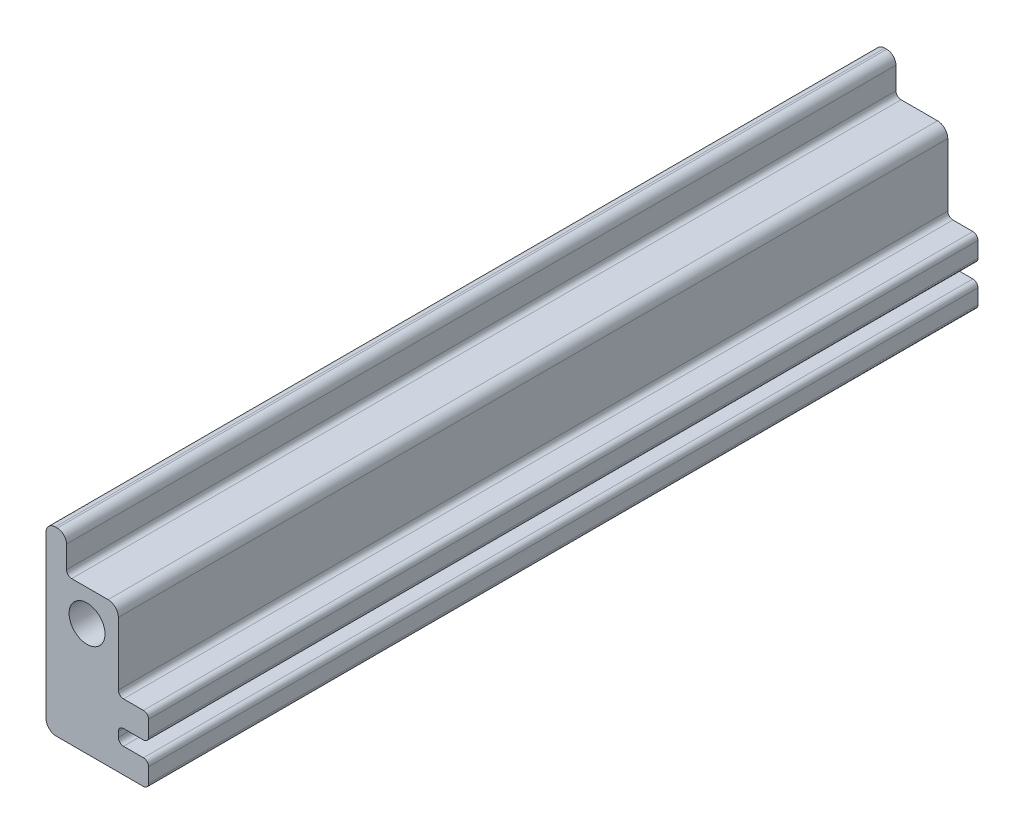
SolidWorks part; units mm, degrees
material "Pink Foam"
ref_plane "Front Plane" through (0, 0, 0) normal (0, 0, 1) x (1, 0, 0)
ref_plane "Top Plane" through (0, 0, 0) normal (0, 1, 0) x (1, 0, 0)
ref_plane "Right Plane" through (0, 0, 0) normal (1, 0, 0) x (0, 0, -1)
sketch "Sketch1" plane through (0, 0, 0) normal (0, 0, 1) x (1, 0, 0)
  line L1 (34.925, -69.85) -> (-19.05, -69.85)
  line L2 (38.1, -41.7472) -> (38.1, -32.2222)
  line L3 (34.925, -29.0472) -> (22.5628, -29.0472)
  line L4 (-25.4, -63.5) -> (-25.4, 36.2978)
  line L6 (19.3878, -25.8722) -> (19.3878, 13.0378)
  line L7 (13.0378, 19.3878) -> (-9.525, 19.3878)
  line L8 (-12.7, 22.5628) -> (-12.7, 36.2978)
  line L9 (-18.415, 42.0128) -> (-19.685, 42.0128)
  line L11 (34.925, -44.9222) -> (22.5628, -44.9222)
  line L12 (11.1125, 0) -> (19.3878, 0) construction
  line L14 (0, 11.1125) -> (0, 19.3878) construction
  line L15 (19.3878, -48.0972) -> (19.3878, -51.2722)
  line L19 (22.5628, -54.4472) -> (34.925, -54.4472)
  line L20 (38.1, -66.675) -> (38.1, -57.6222)
  circle A0 centre (0, 0) radius 11.1125
  arc A3 (-9.525, 19.3878) -> (-12.7, 22.5628) centre (-9.525, 22.5628) cw
  arc A4 (-19.05, -69.85) -> (-25.4, -63.5) centre (-19.05, -63.5) cw
  arc A6 (38.1, -32.2222) -> (34.925, -29.0472) centre (34.925, -32.2222) ccw
  arc A8 (19.3878, 13.0378) -> (13.0378, 19.3878) centre (13.0378, 13.0378) ccw
  arc A9 (-12.7, 36.2978) -> (-18.415, 42.0128) centre (-18.415, 36.2978) ccw
  arc A10 (-19.685, 42.0128) -> (-25.4, 36.2978) centre (-19.685, 36.2978) ccw
  arc A11 (19.3878, -25.8722) -> (22.5628, -29.0472) centre (22.5628, -25.8722) ccw
  arc A12 (22.5628, -44.9222) -> (19.3878, -48.0972) centre (22.5628, -48.0972) ccw
  arc A13 (34.925, -44.9222) -> (38.1, -41.7472) centre (34.925, -41.7472) ccw
  arc A14 (22.5628, -54.4472) -> (19.3878, -51.2722) centre (22.5628, -51.2722) cw
  arc A15 (34.925, -69.85) -> (38.1, -66.675) centre (34.925, -66.675) ccw
  arc A16 (34.925, -54.4472) -> (38.1, -57.6222) centre (34.925, -57.6222) cw
  point P9 (0, -11.1125)
  point P15 (0, 11.1125)
  point P16 (11.1125, 0)
  point P17 (16.2128, -69.85)
  point P26 (16.2128, -69.85)
  point P31 (-12.7, 19.3878)
  point P34 (-25.4, -69.85)
  point P35 (16.2128, -69.85)
  point P37 (32.5, -69.85)
  point P40 (38.1, -29.0472)
  point P42 (26.2491, -69.85)
  point P47 (-12.7, 42.0128)
  point P50 (-25.4, 42.0128)
  point P51 (27.7757, -69.85)
  point P52 (0, 0)
  point P53 (0, 0)
  point P54 (38.9058, -69.85)
  point P56 (19.3878, -54.4472)
  point P59 (38.1, -69.85)
  point P62 (38.1, -54.4472)
  dimension "D1" = 22.225
  dimension "D6" = 8.2753
  dimension "D10" = 3.175
  dimension "D11" = 6.35
  dimension "D12" = 5.715
  dimension "D5" = 3.175
  dimension "D7" = 6.35
  dimension "D13" = 29.0472
  dimension "D14" = 3.175
  dimension "D15" = 18.7122
  dimension "D16" = 3.175
  dimension "D17" = 3.175
  dimension "D18" = 15.875
  dimension "D20" = 3.175
  dimension "D21" = 3.175
  dimension "D22" = 3.175
  dimension "D3" = 69.85
  dimension "D4" = 25.4
  dimension "D8" = 22.625
  dimension "D9" = 12.7
  dimension "D19" = 19.3878
  dimension "D23" = 9.525
extrude "Boss-Extrude1" add sketch "Sketch1" along normal blind 513.461
